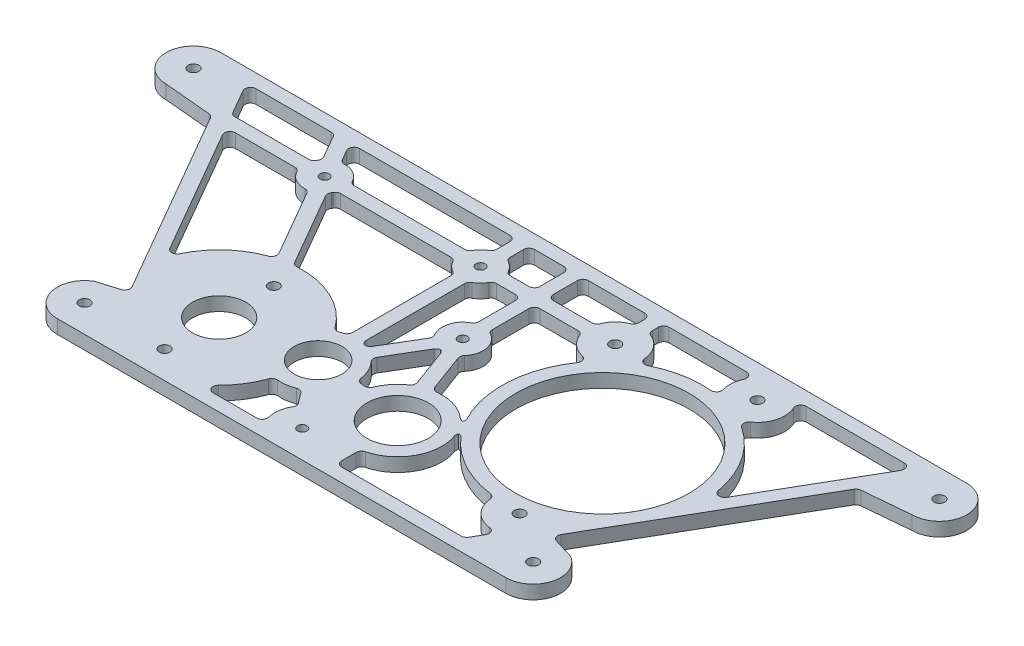
SolidWorks part; units mm, degrees
ref_plane "Front Plane" through (0, 0, 0) normal (0, 0, 1) x (1, 0, 0)
ref_plane "Top Plane" through (0, 0, 0) normal (0, 1, 0) x (1, 0, 0)
ref_plane "Right Plane" through (0, 0, 0) normal (1, 0, 0) x (0, 0, -1)
sketch "Sketch1" plane through (0, 0, 0) normal (0, 1, 0) x (1, 0, 0)
  line L0 (-67.1329, -34.491) -> (-26.9117, -28.6714) construction
  line L1 (-195.4757, -72.591) -> (195.4757, -72.591)
  line L2 (-195.4757, -72.591) -> (-195.4757, 72.591)
  line L3 (-186.1787, 59.891) -> (186.1787, 59.891)
  line L4 (195.4757, -72.591) -> (195.4757, 72.591)
  line L5 (-195.4757, -72.591) -> (195.4757, 72.591) construction
  line L6 (-195.4757, 72.591) -> (195.4757, -72.591) construction
  line L7 (-26.9117, -28.6714) -> (15.8743, -34.491) construction
  line L8 (15.8743, -34.491) -> (-67.1329, -34.491) construction
  line L9 (15.8743, -34.491) -> (72.644, 3.9852) construction
  line L10 (72.644, 3.9852) -> (-26.9117, -28.6714) construction
  line L11 (-166.1463, 72.591) -> (-82.3255, -72.591)
  line L12 (158.814, 72.591) -> (74.9932, -72.591)
  line L13 (-195.4757, 72.591) -> (-180.811, 72.591)
  line L14 (82.3255, -72.591) -> (166.1463, 72.591)
  line L15 (-180.811, 72.591) -> (-96.9902, -72.591) construction
  line L16 (-195.4757, 72.591) -> (-111.6549, -72.591)
  line L17 (96.9902, -72.591) -> (180.811, 72.591) construction
  line L18 (111.6549, -72.591) -> (195.4757, 72.591)
  line L19 (-173.4787, 47.191) -> (-150.2713, 45.0947)
  line L20 (-110.6726, -48.8924) -> (-98.2005, -45.0947)
  line L21 (0, 72.591) -> (0, -72.591) construction
  line L22 (173.4787, 47.191) -> (150.2713, 45.0947)
  line L23 (110.6726, -48.8924) -> (98.2005, -45.0947)
  line L24 (72.644, 3.9852) -> (35.7109, 46.8482) construction
  line L25 (35.7109, 46.8482) -> (91.2979, 57.4018) construction
  line L26 (91.2979, 57.4018) -> (72.644, 3.9852) construction
  line L27 (72.644, 3.9852) -> (81.6718, -43.5654) construction
  line L28 (-173.4787, 72.591) -> (195.4757, 72.591)
  circle A0 centre (-67.1329, -34.491) radius 12.3825
  circle A1 centre (-67.1329, -34.491) radius 32.2072
  circle A2 centre (-67.1329, -9.091) radius 2.4892
  circle A3 centre (-67.1329, -59.891) radius 2.4892
  circle A4 centre (15.8743, -34.491) radius 14.3002
  circle A5 centre (-26.9117, -28.6714) radius 11.1252
  circle A6 centre (72.644, 3.9852) radius 40.3225
  circle A7 centre (-173.4787, 59.891) radius 2.4892
  circle A8 centre (-104.3226, -59.891) radius 2.4892
  circle A9 centre (-173.4787, 59.891) radius 12.7
  circle A10 centre (-104.3226, -59.891) radius 12.7
  circle A11 centre (104.3226, -59.891) radius 2.4892
  circle A12 centre (104.3226, -59.891) radius 12.7
  circle A13 centre (173.4787, 59.891) radius 2.4892
  circle A14 centre (173.4787, 59.891) radius 12.7
  circle A15 centre (35.7109, 46.8482) radius 2.4892
  circle A16 centre (91.2979, 57.4018) radius 2.4892
  circle A17 centre (81.6718, -43.5654) radius 2.4892
  point P0 (0, 0)
  point P16 (-72.4812, -34.491)
  dimension "D1" = 64.4144
  dimension "D2" = 24.765
  dimension "D3" = 4.9784
  dimension "D4" = 25.4
  dimension "D6" = 12.7
  dimension "D11" = 28.6004
  dimension "D14" = 22.2504
  dimension "D15" = 80.645
  dimension "D17" = 50.8
  dimension "D25" = 4.9784
  dimension "D26" = 4.9784
  dimension "D27" = 12.7
  dimension "D28" = 25.4
  dimension "D30" = 25.4
  dimension "D36" = 4.9784
  dimension "D37" = 4.9784
  dimension "D38" = 4.9784
  dimension "D7" = 25.4
  dimension "D8" = 40.64
  dimension "D9" = 43.18
  dimension "D10" = 83.0072
  dimension "D12" = 68.58
  dimension "D13" = 104.775
  dimension "D16" = 120
  dimension "D18" = 120
  dimension "D19" = 12.7
  dimension "D20" = 6.35
  dimension "D21" = 12.7
  dimension "D22" = 12.7
  dimension "D23" = 12.7
  dimension "D24" = 12.7
  dimension "D29" = 31.75
  dimension "D31" = 31.75
  dimension "D32" = 56.58
  dimension "D33" = 48.4
  dimension "D34" = 150
  dimension "D35" = 10.75
  dimension "D39" = 390.9515
  dimension "D40" = 372.3574
  dimension "D41" = 145.1819
  dimension "D42" = 107.0819
  dimension "D43" = 23.3018
  dimension "D44" = 125.161
  dimension "D5" = 2
extrude "Boss-Extrude1" add sketch "Sketch1" along normal blind 6.35 contours L3 A16 L11 A1 A5 L1 L12 A6 A17 A15 A4 | A9 L19 L11 L3 | A9 L3 A7 | L3 A9 A7 | A9 L11 L28 | A9 L3 L11 | L28 L11 L3 L12 | A14 L3 A13 | L22 A14 L3 L14 | L1 L14 L3 L12 | L28 L12 L3 L14 | L3 A14 L14 | L14 A14 L28 | A14 L3 A13 | A12 L23 A11 | L14 A12 L23 | L1 A12 L14 | A5 A1 A3 A2 A0 | A10 L20 A8 | A10 L1 L11 | A10 L11 L20 region at (-90.4145, 0, 67.9208) region at (-110.493, 0, 70.5784) region at (-173.4787, 0, -54.3278) region at (-80.2961, 0, 6.0972) region at (-12.5567, 0, -6.9871) region at (-173.4787, 0, -65.4541) region at (-159.3373, 0, -50.5787) region at (116.9036, 0, 6.35) region at (-98.9155, 0, 47.5186) region at (-166.9156, 0, -71.2586) region at (-160.3524, 0, -61.5233) region at (90.4145, 0, 67.9208) region at (-3.6662, 0, -66.2898) region at (93.6351, 0, 66.0614) region at (98.9155, 0, 47.5186) region at (158.814, 0, -66.241) region at (160.3524, 0, -61.5233) region at (159.3373, 0, -50.5787) region at (166.9156, 0, -71.2586) region at (173.4787, 0, -54.3278) region at (173.4787, 0, -65.4541)
sketch "Sketch2" plane through (0, 6.35, 0) normal (0, 1, 0) x (1, 0, 0)
  line L0 (-150.2713, 45.0947) -> (-98.2005, -45.0947)
  line L1 (-158.814, 72.591) -> (-74.9932, -72.591)
  line L2 (-173.4787, 72.591) -> (173.4787, 72.591) construction
  line L3 (-104.3226, -72.591) -> (104.3226, -72.591) construction
  line L4 (-155.1478, 66.241) -> (155.1478, 66.241)
  line L5 (-78.6593, -66.241) -> (78.6593, -66.241)
  line L6 (150.2713, 45.0947) -> (98.2005, -45.0947)
  line L7 (158.814, 72.591) -> (74.9932, -72.591)
  line L8 (-26.9117, -28.6714) -> (-26.9117, 66.241) construction
  line L9 (-26.9117, -28.6714) -> (15.8743, -34.491) construction
  line L10 (15.8743, -34.491) -> (72.644, 3.9852) construction
  line L11 (35.7109, 46.8482) -> (35.7109, 66.241) construction
  line L12 (15.8743, -34.491) -> (15.8743, -66.241) construction
  line L13 (-67.1329, -9.091) -> (-110.6258, 66.241) construction
  line L14 (-143.9514, 46.8482) -> (35.7109, 46.8482) construction
  line L15 (-26.9117, -28.6714) -> (-3.1757, -59.7979) construction
  line L16 (-145.7845, 50.0232) -> (23.4142, 50.0232)
  line L17 (-142.1183, 43.6732) -> (23.4142, 43.6732)
  line L18 (-114.292, 66.241) -> (-77.5651, 2.6281)
  line L19 (-106.9596, 66.241) -> (-70.9535, 3.8765)
  line L20 (-30.0867, 66.241) -> (-30.0867, -11.487)
  line L21 (-23.7367, 66.241) -> (-23.7367, -11.487)
  line L22 (-19.0162, -44.2612) -> (-13.1568, -51.9451)
  line L23 (-8.1074, -48.0946) -> (-13.9669, -40.4108)
  line L24 (-9.4562, -27.8414) -> (-3.9163, -28.5949)
  line L25 (-10.3121, -34.1334) -> (-4.7721, -34.887)
  line L26 (12.6993, -54.8956) -> (12.6993, -66.241)
  line L27 (19.0493, -54.8956) -> (19.0493, -66.241)
  line L28 (30.9837, -20.4149) -> (32.3173, -19.5111)
  line L29 (34.5464, -25.6713) -> (35.8799, -24.7675)
  line L30 (32.5359, 59.145) -> (32.5359, 66.241)
  line L31 (38.8859, 59.145) -> (38.8859, 66.241)
  line L32 (36.5245, 66.241) -> (36.5245, -72.591) construction
  line L33 (30.1745, 66.241) -> (30.1745, -72.591) construction
  line L34 (30.1745, -19.5935) -> (-23.7367, 66.241) construction
  line L35 (18.2805, -13.9814) -> (-32.1059, 66.241) construction
  line L36 (-17.9315, 43.6732) -> (18.2805, -13.9814)
  line L37 (0.1745, 14.8459) -> (-23.7367, -0.1724) construction
  line L38 (-1.8899, 13.5493) -> (-1.8899, 66.241) construction
  line L39 (-1.8899, 13.5493) -> (-26.9117, -28.6714) construction
  line L40 (-1.8899, 13.5493) -> (15.8743, -34.491) construction
  line L41 (-5.0649, 66.241) -> (-5.0649, 22.5296)
  line L42 (1.2851, 66.241) -> (1.2851, 22.5296)
  line L43 (-9.1997, 7.4426) -> (-20.8819, -12.2694)
  line L44 (-3.737, 4.2051) -> (-15.4192, -15.5069)
  line L45 (-1.7532, 4.0253) -> (5.8195, -16.454)
  line L46 (4.2026, 6.2276) -> (11.7754, -14.2517)
  circle A0 centre (-67.1329, -34.491) radius 38.5572
  circle A1 centre (72.644, 3.9852) radius 46.6725
  circle A2 centre (-26.9117, -28.6714) radius 17.4752
  circle A3 centre (15.8743, -34.491) radius 20.6502
  circle A4 centre (35.7109, 46.8482) radius 12.7
  circle A5 centre (91.2979, 57.4018) radius 12.7
  circle A6 centre (81.6718, -43.5654) radius 12.7
  circle A7 centre (-99.4294, 46.8482) radius 2.1526
  circle A8 centre (-26.9117, 46.8482) radius 2.1527
  circle A9 centre (-99.4294, 46.8482) radius 9.525
  circle A10 centre (-26.9117, 46.8482) radius 9.525
  circle A11 centre (-3.1757, -59.7979) radius 12.7
  circle A12 centre (-3.1757, -59.7979) radius 2.1527
  circle A13 centre (-1.8899, 13.5493) radius 9.525
  circle A14 centre (-1.8899, 13.5493) radius 2.1526
  point P96 (-17.9315, 43.6732)
  dimension "D1" = 77.1144
  dimension "D4" = 93.345
  dimension "D7" = 34.9504
  dimension "D8" = 41.3004
  dimension "D9" = 25.4
  dimension "D10" = 25.4
  dimension "D11" = 25.4
  dimension "D12" = 4.3053
  dimension "D13" = 4.3053
  dimension "D14" = 19.05
  dimension "D15" = 19.05
  dimension "D17" = 25.4
  dimension "D18" = 4.3053
  dimension "D28" = 75.5196
  dimension "D31" = 19.05
  dimension "D35" = 4.3053
  dimension "D2" = 6.35
  dimension "D3" = 6.35
  dimension "D5" = 6.35
  dimension "D6" = 6.35
  dimension "D16" = 19.05
  dimension "D19" = 12.793
  dimension "D20" = 6.35
  dimension "D21" = 6.35
  dimension "D22" = 6.35
  dimension "D23" = 6.35
  dimension "D24" = 6.35
  dimension "D25" = 6.35
  dimension "D26" = 6.35
  dimension "D27" = 6.35
  dimension "D29" = 1.7536
  dimension "D30" = 6.35
  dimension "D32" = 6.35
  dimension "D33" = 6.35
  dimension "D34" = 6.35
extrude "Cut-Extrude1" cut sketch "Sketch2" against normal through all contours A9 L17 L1 A0 L18 | A9 L18 L4 L1 L16 | A10 L20 L4 L19 A9 L16 | A10 L17 A9 L19 A0 A2 L20 | A10 L21 A2 L24 A3 L28 A1 A4 L17 | A5 L4 L31 A4 A1 | A5 A1 L7 L4 | A6 A1 L29 A3 L27 L5 L7 | A11 L22 A2 A0 L5 | A7 | A8 | A12 | A10 L16 L41 L4 L21 | L41 L17 L36 | A13 L41 L36 A10 L21 A2 L43 | A13 L44 A2 L24 A3 L45 | A13 L46 A3 L36 | A4 L30 L4 L42 L16 | A14 region at (-130.2376, 6.35, -58.1926) region at (-108.4613, 6.35, -17.2209) region at (-65.7948, 6.35, -58.6288) region at (-13.8438, 6.35, -58.593) region at (-25.9719, 6.35, 57.1796) region at (-55.0068, 6.35, -22.2139) region at (15.386, 6.35, -58.7048) region at (-9.3537, 6.35, -36.8447) region at (-17.2275, 6.35, -16.8941) region at (60.1942, 6.35, -57.9969) region at (17.1957, 6.35, -18.3194) region at (49.3507, 6.35, 53.2524) region at (-4.6206, 6.35, 13.136) region at (123.9014, 6.35, -45.8865) region at (10.9694, 6.35, 5.9698) region at (-99.4294, 6.35, -46.8482) region at (-26.9117, 6.35, -46.8482) region at (-3.1757, 6.35, 59.7979) region at (-1.8899, 6.35, -13.5493)
fillet "Fillet1" radius 2.54 79 edges at (119.3161, 3.175, -4.1787) (35.8799, 3.175, 24.7675) (32.3173, 3.175, 19.5111) (30.9837, 3.175, 20.4149) (-3.9163, 3.175, 28.5949) (-9.4562, 3.175, 27.8414) (37.0917, 3.175, -34.2235) (32.5359, 3.175, -66.241) (-19.0162, 3.175, 44.2612) (-34.9999, 3.175, 13.1806) (-30.0867, 3.175, 11.487) (-90.4491, 3.175, -50.0232) (-101.1699, 3.175, -56.2129) (-70.9535, 3.175, -3.8765) (-103.8268, 3.175, 22.6497) (-30.0867, 3.175, -66.241) (82.1788, 3.175, -66.241) (69.0128, 3.175, 42.5458) (84.6189, 3.175, 55.9187) (155.1478, 3.175, -66.241) (23.4142, 3.175, -43.6732) (-30.0867, 3.175, -37.868) (-35.892, 3.175, -43.6732) (-97.6889, 3.175, -37.4836) (-108.4097, 3.175, -43.6732) (-114.292, 3.175, -66.241) (-150.2713, 3.175, -45.0947) (81.055, 3.175, -49.8936) (32.5359, 3.175, -59.145) (23.4142, 3.175, -50.0232) (-30.0867, 3.175, -55.8285) (-35.892, 3.175, -50.0232) (-106.6692, 3.175, -53.0379) (-108.4097, 3.175, -50.0232) (-77.5651, 3.175, -2.6281) (78.6593, 3.175, 66.241) (-13.1568, 3.175, 51.9451) (-14.12, 3.175, 66.241) (-98.2005, 3.175, 45.0947) (19.0493, 3.175, 66.241) (-45.2561, 3.175, 66.241) (-145.7845, 3.175, -50.0232) (-17.9315, 3.175, -50.0232) (47.9928, 3.175, -43.6165) (150.2713, 3.175, -45.0947) (98.2005, 3.175, 45.0947) (100.4171, 3.175, -66.241) (94.6401, 3.175, -45.1494) (38.8859, 3.175, -59.145) (38.8859, 3.175, -66.241) (34.5464, 3.175, 25.6713) (19.0493, 3.175, 54.8956) (-23.7367, 3.175, -55.8285) (-23.7367, 3.175, -66.241) (-17.9315, 3.175, -43.6732) (-23.7367, 3.175, -37.868) (-23.7367, 3.175, 11.487) (-30.2774, 3.175, 45.8194) (-90.4491, 3.175, -43.6732) (-92.1896, 3.175, -40.6586) (-106.9596, 3.175, -66.241) (-142.1183, 3.175, -43.6732) (-155.1478, 3.175, -66.241) (-20.8819, 3.175, 12.2694) (-9.1997, 3.175, -7.4426) (-3.737, 3.175, -4.2051) (-1.7532, 3.175, -4.0253) (-15.4192, 3.175, 15.5069) (-5.0649, 3.175, -22.5296) (5.8195, 3.175, 16.454) (-5.0649, 3.175, -43.6732) (1.2851, 3.175, -43.6732) (1.2851, 3.175, -22.5296) (4.2026, 3.175, -6.2276) (11.7754, 3.175, 14.2517) (-5.0649, 3.175, -66.241) (1.2851, 3.175, -66.241) (-5.0649, 3.175, -50.0232) (1.2851, 3.175, -50.0232)
